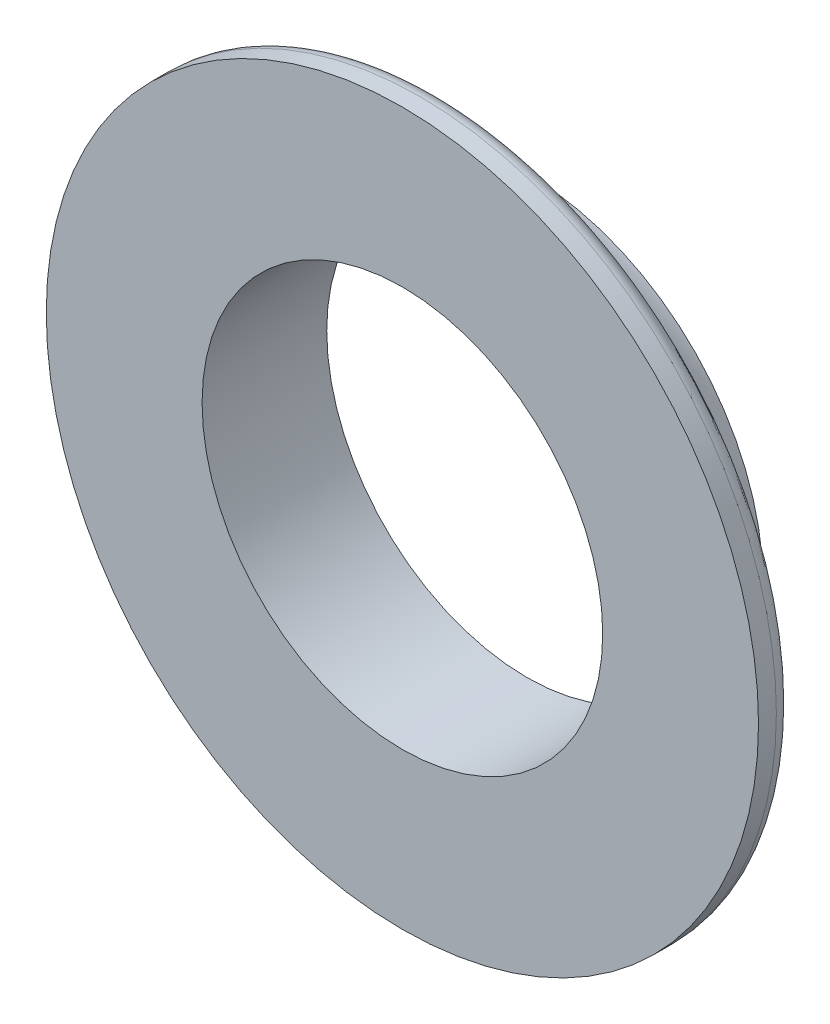
SolidWorks part; units mm, degrees
ref_plane "Front Plane" through (0, 0, 0) normal (0, 0, 1) x (1, 0, 0)
ref_plane "Top Plane" through (0, 0, 0) normal (0, 1, 0) x (1, 0, 0)
ref_plane "Right Plane" through (0, 0, 0) normal (1, 0, 0) x (0, 0, -1)
sketch "Sketch1" plane through (0, 0, 0) normal (0, 0, 1) x (1, 0, 0)
  circle A0 centre (0, 0) radius 11.25
  circle A1 centre (0, 0) radius 13.25
  dimension "D1" = 2
extrude "Boss-Extrude1" add sketch "Sketch1" along normal blind 7
sketch "Sketch2" plane through (0, 0, 7) normal (0, 0, 1) x (1, 0, 0)
  circle A0 centre (0, 0) radius 20
extrude "Boss-Extrude2" add sketch "Sketch2" against normal blind 2
fillet "Fillet1" radius 6 1 edges at (13.25, 0, 5)
sketch "Sketch3" plane through (0, 0, 5) normal (0, 0, -1) x (-1, 0, 0)
  circle A0 centre (0, 0) radius 11.25 construction
  circle A1 centre (0, 0) radius 11.25
extrude "Cut-Extrude1" cut sketch "Sketch3" against normal blind 2
fillet "Fillet2" radius 1 1 edges at (20, 0, 5)
